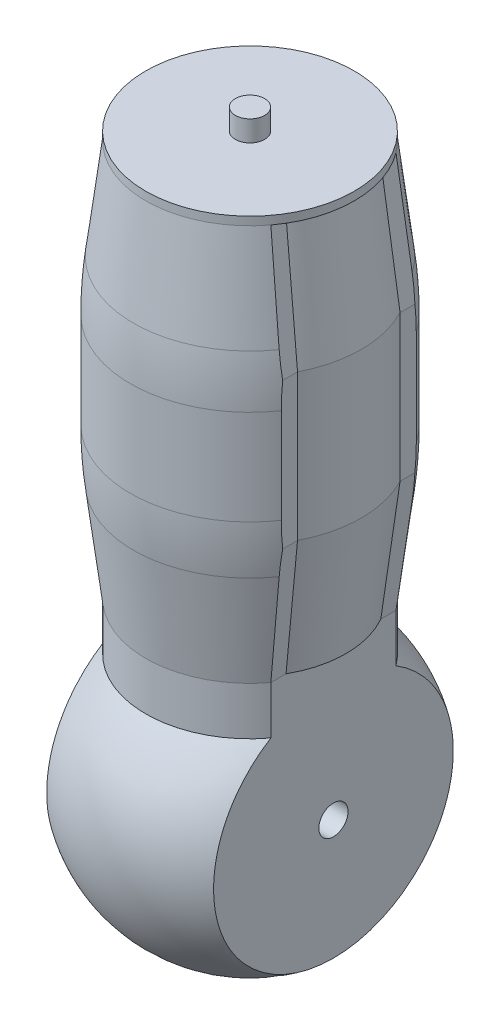
SolidWorks part; units mm, degrees
material "1060 Alloy"
ref_plane "Front Plane" through (0, 0, 0) normal (0, 0, 1) x (1, 0, 0)
ref_plane "Top Plane" through (0, 0, 0) normal (0, 1, 0) x (1, 0, 0)
ref_plane "Right Plane" through (0, 0, 0) normal (1, 0, 0) x (0, 0, -1)
sketch "Sketch1" plane through (0, 0, 0) normal (0, 1, 0) x (1, 0, 0)
  line L0 (0, 35) -> (0, -35) construction
  line L1 (0, 35) -> (0, -35)
  arc A0 (0, -35) -> (0, 35) centre (0, 0) ccw
  dimension "D1" = 70
revolve "Revolve2" add sketch "Sketch1" angle 360 about L0
sketch "Sketch2" plane through (0, 0, 0) normal (0, 1, 0) x (1, 0, 0)
  line L2 (-20, -28.7228) -> (-20, 28.7228)
  line L4 (20, -28.7228) -> (20, 28.7228)
  line L5 (-20, -35) -> (20, 35) construction
  line L6 (-20, 35) -> (20, -35) construction
  arc A0 (20, 28.7228) -> (-20, 28.7228) centre (0, 0) ccw
  arc A1 (-20, -28.7228) -> (20, -28.7228) centre (0, 0) ccw
  dimension "D1" = 40
extrude "Cut-Extrude1" cut sketch "Sketch2" against normal up to surface and the other way up to next flip side to cut
sketch "Sketch3" plane through (0, 0, 0) normal (0, 1, 0) x (1, 0, 0)
  line L4 (20, -28.7228) -> (20, 28.7228) construction
  line L6 (-20, 15) -> (-20, -15)
  line L8 (20, 15) -> (20, -15)
  line L9 (-20, 26.2775) -> (20, -26.2775) construction
  line L10 (-20, -26.2775) -> (20, 26.2775) construction
  arc A3 (20, 15) -> (-20, 15) centre (0, 0) ccw
  arc A4 (-20, -15) -> (20, -15) centre (0, 0) ccw
  circle A6 centre (0, 0) radius 35 construction
  dimension "D1" = 50
  dimension "D2" = 10
extrude "Boss-Extrude1" add sketch "Sketch3" along normal blind 36
sketch "Sketch4" plane through (-20, 0, 0) normal (-1, 0, 0) x (0, 0, 1)
  circle A0 centre (0, 0) radius 3.5
  dimension "D1" = 7
extrude "Cut-Extrude2" cut sketch "Sketch4" against normal blind 5
pattern_linear "LPattern1" count 2 spacing 35 along (1, 0, 0) of "Cut-Extrude2"
sketch "Sketch5" plane through (0, 36, 0) normal (0, 1, 0) x (1, 0, 0)
  line L0 (-20, 15) -> (-20, 11.3578)
  line L1 (-20, 15) -> (-20, -15) construction
  line L2 (-20, -15) -> (-20, -11.3578)
  line L3 (20, 15) -> (20, 11.3578)
  line L4 (20, -11.3578) -> (20, -15)
  arc A0 (-20, -15) -> (20, -15) centre (0, 0) ccw
  arc A1 (20, -11.3578) -> (20, 11.3578) centre (0, 0) ccw
  arc A2 (20, 15) -> (-20, 15) centre (0, 0) ccw
  arc A3 (-20, 11.3578) -> (-20, -11.3578) centre (0, 0) ccw
  dimension "D2" = 46
extrude "Boss-Extrude2" add sketch "Sketch5" along normal blind 30 draft 7 draft outward yes
sketch "Sketch9" plane through (0, 66, 0) normal (0, 1, 0) x (1, 0, 0)
  line L4 (23.6835, 12.2923) -> (23.6835, 16.1813)
  line L5 (-23.6835, 16.1813) -> (-23.6835, 12.2923)
  line L6 (-23.6835, -12.2923) -> (-23.6835, -16.1813)
  line L7 (23.6835, -16.1813) -> (23.6835, -12.2923)
  line L8 (23.6835, 12.2923) -> (23.6835, 16.1813)
  line L9 (-23.6835, 16.1813) -> (-23.6835, 12.2923)
  line L10 (-23.6835, -12.2923) -> (-23.6835, -16.1813)
  line L11 (23.6835, -16.1813) -> (23.6835, -12.2923)
  arc A4 (23.6835, -12.2923) -> (23.6835, 12.2923) centre (0, 0) ccw
  arc A5 (23.6835, 16.1813) -> (-23.6835, 16.1813) centre (0, 0) ccw
  arc A6 (-23.6835, 12.2923) -> (-23.6835, -12.2923) centre (0, 0) ccw
  arc A7 (-23.6835, -16.1813) -> (23.6835, -16.1813) centre (0, 0) ccw
  arc A8 (23.6835, -12.2923) -> (23.6835, 12.2923) centre (0, 0) ccw
  arc A9 (23.6835, 16.1813) -> (-23.6835, 16.1813) centre (0, 0) ccw
  arc A10 (-23.6835, 12.2923) -> (-23.6835, -12.2923) centre (0, 0) ccw
  arc A11 (-23.6835, -16.1813) -> (23.6835, -16.1813) centre (0, 0) ccw
  dimension "D1" = 0
extrude "Boss-Extrude6" add sketch "Sketch9" along normal blind 35
sketch "Sketch12" plane through (0, 101, 0) normal (0, 1, 0) x (1, 0, 0)
  line L4 (23.6835, 12.2923) -> (23.6835, 16.1813)
  line L5 (-23.6835, 16.1813) -> (-23.6835, 12.2923)
  line L6 (-23.6835, -12.2923) -> (-23.6835, -16.1813)
  line L7 (23.6835, -16.1813) -> (23.6835, -12.2923)
  line L8 (23.6835, 12.2923) -> (23.6835, 16.1813)
  line L9 (-23.6835, 16.1813) -> (-23.6835, 12.2923)
  line L10 (-23.6835, -12.2923) -> (-23.6835, -16.1813)
  line L11 (23.6835, -16.1813) -> (23.6835, -12.2923)
  arc A4 (23.6835, -12.2923) -> (23.6835, 12.2923) centre (0, 0) ccw
  arc A5 (23.6835, 16.1813) -> (-23.6835, 16.1813) centre (0, 0) ccw
  arc A6 (-23.6835, 12.2923) -> (-23.6835, -12.2923) centre (0, 0) ccw
  arc A7 (-23.6835, -16.1813) -> (23.6835, -16.1813) centre (0, 0) ccw
  arc A8 (23.6835, -12.2923) -> (23.6835, 12.2923) centre (0, 0) ccw
  arc A9 (23.6835, 16.1813) -> (-23.6835, 16.1813) centre (0, 0) ccw
  arc A10 (-23.6835, 12.2923) -> (-23.6835, -12.2923) centre (0, 0) ccw
  arc A11 (-23.6835, -16.1813) -> (23.6835, -16.1813) centre (0, 0) ccw
  dimension "D1" = 0
extrude "Boss-Extrude9" add sketch "Sketch12" along normal blind 30 draft 7
sketch "Sketch10" plane through (0, 131, 0) normal (0, 1, 0) x (1, 0, 0)
  circle A0 centre (0, 0) radius 25
  dimension "D1" = 50
extrude "Boss-Extrude7" add sketch "Sketch10" along normal blind 2
sketch "Sketch11" plane through (0, 133, 0) normal (0, 1, 0) x (1, 0, 0)
  circle A0 centre (0, 0) radius 3.5
  dimension "D1" = 7
extrude "Boss-Extrude8" add sketch "Sketch11" along normal blind 5
fillet "Fillet3" radius 100 4 edges at (0, 66, -28.6835) (0, 101, -28.6835) (0, 101, 28.6835) (0, 66, 28.6835)
